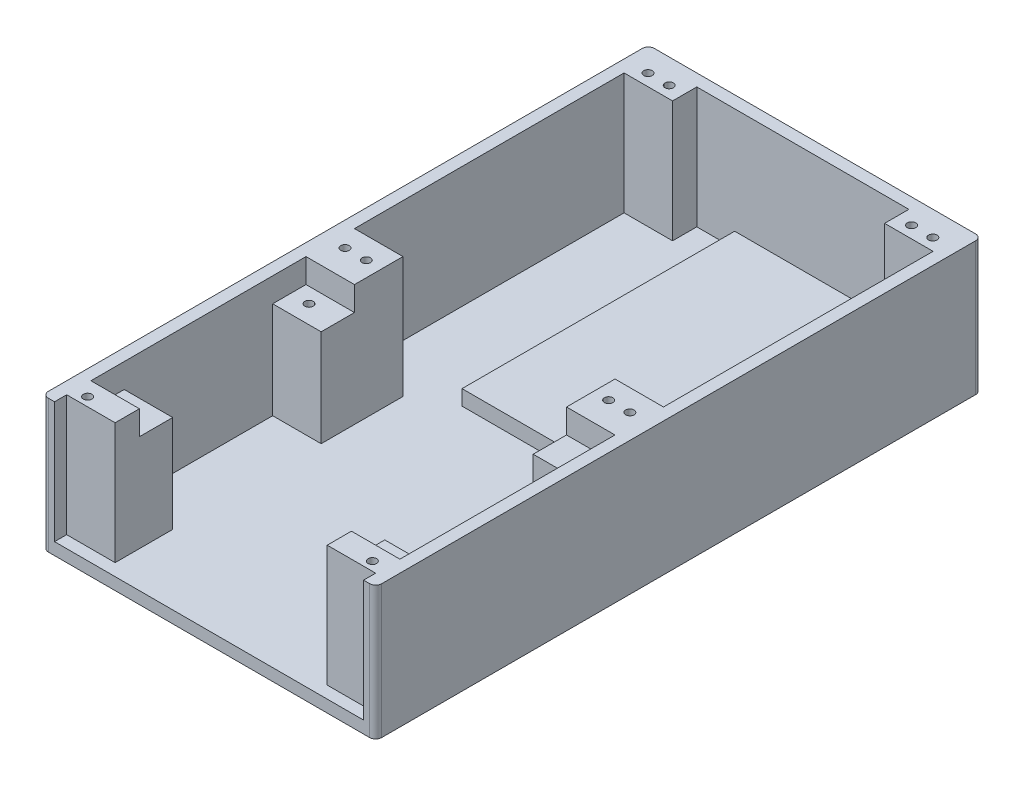
SolidWorks part; units mm, degrees
ref_plane "Front Plane" through (0, 0, 0) normal (0, 0, 1) x (1, 0, 0)
ref_plane "Top Plane" through (0, 0, 0) normal (0, 1, 0) x (1, 0, 0)
ref_plane "Right Plane" through (0, 0, 0) normal (1, 0, 0) x (0, 0, -1)
sketch "Sketch1" plane through (0, 0, 0) normal (0, 1, 0) x (1, 0, 0)
  line L1 (0, 0) -> (139.7, 0)
  line L2 (0, 0) -> (0, 254)
  line L3 (0, 254) -> (139.7, 254)
  line L4 (139.7, 0) -> (139.7, 254)
  dimension "D1" = 254
  dimension "D2" = 139.7
extrude "Base" add sketch "Sketch1" along normal blind 5.08
sketch "Sketch2" plane through (0, 5.08, 0) normal (0, 1, 0) x (1, 0, 0)
  line L1 (0, 254) -> (139.7, 254)
  line L2 (0, 254) -> (0, 0)
  line L3 (0, 0) -> (139.7, 0)
  line L4 (139.7, 254) -> (139.7, 0)
  line L5 (5.08, 248.92) -> (134.62, 248.92)
  line L6 (5.08, 248.92) -> (5.08, 5.08)
  line L7 (5.08, 5.08) -> (134.62, 5.08)
  line L8 (134.62, 248.92) -> (134.62, 5.08)
  line M9 (0, 254) -> (0, 0)
  line M10 (0, 0) -> (139.7, 0)
  line M11 (139.7, 0) -> (139.7, 254)
  line M12 (139.7, 254) -> (0, 254)
  dimension "D1" = 5.08
  dimension "D2" = 5.08
  dimension "D3" = 5.08
  dimension "D4" = 5.08
extrude "Walls" add sketch "Sketch2" along normal blind 50.8 contours L5 L8 L7 L6 M12 M9 M10 M11 region at (69.85, 5.08, -251.1012)
ref_plane "Plane1" through (0, 0, -60.96) normal (0, 0, 1) x (1, 0, 0)
sketch "Sketch4" plane through (0, 0, 0) normal (0, 0, 1) x (1, 0, 0)
  line L0 (0, 0) -> (139.7, 0) construction
  line L1 (5.08, 55.88) -> (134.62, 55.88)
  line L2 (5.08, 55.88) -> (5.08, 5.08)
  line L3 (5.08, 5.08) -> (134.62, 5.08)
  line L4 (134.62, 55.88) -> (134.62, 5.08)
  line L5 (0, 55.88) -> (0, 0) construction
  line L6 (139.7, 55.88) -> (139.7, 0) construction
  line L7 (0, 55.88) -> (139.7, 55.88) construction
  dimension "D1" = 5.08
  dimension "D2" = 5.08
  dimension "D3" = 5.08
  dimension "D4" = 0
extrude "Bottom Cut" cut sketch "Sketch4" against normal blind 139.7
sketch "Sketch12" plane through (0, 5.08, 0) normal (0, 1, 0) x (1, 0, 0)
  line L0 (139.7, 254) -> (0, 254) construction
  line L1 (134.62, 248.92) -> (114.3, 248.92)
  line L2 (134.62, 248.92) -> (134.62, 238.76)
  line L3 (134.62, 238.76) -> (114.3, 238.76)
  line L4 (114.3, 248.92) -> (114.3, 238.76)
  line L5 (139.7, 0) -> (139.7, 254) construction
  line L7 (5.08, 248.92) -> (25.4, 248.92)
  line L8 (5.08, 248.92) -> (5.08, 238.76)
  line L9 (5.08, 238.76) -> (25.4, 238.76)
  line L10 (25.4, 248.92) -> (25.4, 238.76)
  line L11 (134.62, 105.41) -> (114.3, 105.41)
  line L12 (134.62, 105.41) -> (134.62, 125.73)
  line L13 (134.62, 125.73) -> (114.3, 125.73)
  line L14 (114.3, 105.41) -> (114.3, 125.73)
  line L15 (5.08, 105.41) -> (25.4, 105.41)
  line L16 (5.08, 105.41) -> (5.08, 125.73)
  line L17 (5.08, 125.73) -> (25.4, 125.73)
  line L18 (25.4, 105.41) -> (25.4, 125.73)
  dimension "D1" = 15.24
  dimension "D2" = 25.4
  dimension "D3" = 20.32
extrude "Mounting Struts" add sketch "Sketch12" along normal up to surface (50.8 mm away) up to face at (69.85, 55.88, -125.73)
sketch "Sketch13" plane through (0, 55.88, 0) normal (0, 1, 0) x (1, 0, 0)
  line L0 (139.7, 254) -> (0, 254) construction
  line L1 (139.7, 0) -> (139.7, 254) construction
  circle A0 centre (120.65, 243.713) radius 1.778
  circle A1 centre (19.05, 243.713) radius 1.778
  circle A2 centre (120.65, 116.713) radius 1.778
  circle A3 centre (19.05, 116.713) radius 1.778
  dimension "D1" = 3.556
  dimension "D2" = 10.287
  dimension "D3" = 19.05
  dimension "D4" = 101.6
  dimension "D5" = 127
extrude "Panel Mounting Holes" cut sketch "Sketch13" against normal blind 12.7
sketch "Sketch14" plane through (0, 53.848, 0) normal (0, 1, 0) x (1, 0, 0)
  line L1 (134.62, 5.08) -> (114.3, 5.08)
  line L2 (134.62, 5.08) -> (134.62, 15.24)
  line L3 (134.62, 15.24) -> (114.3, 15.24)
  line L4 (114.3, 5.08) -> (114.3, 15.24)
  line L5 (5.08, 5.08) -> (25.4, 5.08)
  line L6 (5.08, 5.08) -> (5.08, 15.24)
  line L7 (5.08, 15.24) -> (25.4, 15.24)
  line L8 (25.4, 5.08) -> (25.4, 15.24)
  dimension "D1" = 10.16
  dimension "D2" = 20.32
extrude "Boss-Extrude6" add sketch "Sketch14" along normal up to surface and the other way up to surface up to face at (19.05, 55.88, -241.935) other way up to face at (69.85, 5.08, -148.59)
sketch "Sketch17" plane through (0, 55.88, 0) normal (0, 1, 0) x (1, 0, 0)
  line L0 (139.7, 0) -> (139.7, 254) construction
  line L1 (0, -30.734) -> (0, 30.734) construction
  circle A0 centre (129.54, 243.713) radius 1.778
  circle A1 centre (10.16, 243.713) radius 1.778
  circle A2 centre (10.16, 116.713) radius 1.778
  circle A3 centre (129.54, 116.713) radius 1.778
  circle A4 centre (129.54, 8.763) radius 1.778
  circle A5 centre (10.16, 8.763) radius 1.778
  circle A7 centre (120.65, 116.713) radius 1.778 construction
  circle A8 centre (19.05, 116.713) radius 1.778 construction
  circle A9 centre (19.05, 243.713) radius 1.778 construction
  circle A10 centre (120.65, 243.713) radius 1.778 construction
  dimension "D1" = 3.556
  dimension "D2" = 10.16
  dimension "D3" = 10.16
  dimension "D4" = 127
  dimension "D5" = 107.95
extrude "Front Mounting Holes" cut sketch "Sketch17" against normal blind 12.7
fillet "Corner Fillet" radius 2.54 4 edges at (0, 27.94, 0) (139.7, 27.94, 0) (0, 27.94, -254) (139.7, 27.94, -254)
sketch "Sketch18" plane through (0, 5.08, 0) normal (0, 1, 0) x (1, 0, 0)
  line L0 (25.4, 105.41) -> (25.4, 125.73) construction
  line L1 (5.08, 105.41) -> (25.4, 105.41)
  line L2 (5.08, 105.41) -> (5.08, 91.44)
  line L3 (5.08, 91.44) -> (25.4, 91.44)
  line L4 (25.4, 105.41) -> (25.4, 91.44)
  line L5 (134.62, 105.41) -> (114.3, 105.41)
  line L6 (134.62, 105.41) -> (134.62, 91.44)
  line L7 (134.62, 91.44) -> (114.3, 91.44)
  line L8 (114.3, 105.41) -> (114.3, 91.44)
  line L9 (134.62, 15.24) -> (114.3, 15.24)
  line L10 (134.62, 15.24) -> (134.62, 29.21)
  line L11 (134.62, 29.21) -> (114.3, 29.21)
  line L12 (114.3, 15.24) -> (114.3, 29.21)
  line L13 (5.08, 15.24) -> (25.4, 15.24)
  line L14 (5.08, 15.24) -> (5.08, 29.21)
  line L15 (5.08, 29.21) -> (25.4, 29.21)
  line L16 (25.4, 15.24) -> (25.4, 29.21)
  line L17 (114.3, 125.73) -> (114.3, 105.41) construction
  dimension "D1" = 13.97
extrude "Boss-Extrude8" add sketch "Sketch18" along normal blind 40.64
sketch "Sketch19" plane through (0, 45.72, 0) normal (0, 1, 0) x (1, 0, 0)
  line L0 (114.3, 105.41) -> (134.62, 105.41) construction
  line L1 (134.62, 105.41) -> (134.62, 15.24) construction
  line L2 (5.08, 15.24) -> (25.4, 15.24) construction
  line L3 (5.08, 105.41) -> (5.08, 15.24) construction
  circle A0 centre (12.7, 99.06) radius 1.778
  circle A1 centre (127, 99.06) radius 1.778
  circle A2 centre (127, 21.59) radius 1.778
  circle A3 centre (12.7, 21.59) radius 1.778
  dimension "D1" = 3.556
  dimension "D2" = 6.35
  dimension "D3" = 7.62
  dimension "D4" = 6.35
  dimension "D5" = 7.62
extrude "Cut-Extrude1" cut sketch "Sketch19" against normal blind 12.7
sketch "Sketch20" plane through (0, 5.08, 0) normal (0, 1, 0) x (1, 0, 0)
  line L0 (25.4, 248.92) -> (114.3, 248.92) construction
  line L1 (98.425, 248.92) -> (41.275, 248.92)
  line L2 (98.425, 248.92) -> (98.425, 134.62)
  line L3 (98.425, 134.62) -> (41.275, 134.62)
  line L4 (41.275, 248.92) -> (41.275, 134.62)
  line L6 (25.4, 238.76) -> (114.3, 238.76) construction
  point P10 (69.85, 238.76)
  point P11 (69.85, 248.92)
  dimension "D1" = 57.15
  dimension "D2" = 114.3
other "AlignGroup1"
extrude "Boss-Extrude9" add sketch "Sketch20" along normal blind 6.35
equation "\"Arrow Height\"= 1.5in"
equation "\"Button Height\"= 2in"
equation "\"Button Width\"= 4in"
equation "\"Haptic Diameter\"= 10mm"
equation "\"Haptic Thickness\"= 2.7mm"
equation "\"Arrow Spacing\"= 1in"
equation "\"Arrow Width\"= 1in"
equation "\"Haptic Wire Angle\"= 63.43"
equation "\"Haptic Wire Width\"= .1in"
equation "\"Haptic Wire Height\"= .15in"
equation "\"Mounting Bolt Hole Diameter\"= .14in"
equation "\"D1@Sketch13\"=\"Mounting Bolt Hole Diameter\""
equation "\"D1@Sketch17\"=\"Mounting Bolt Hole Diameter\""
equation "\"D1@Sketch19\"=\"Mounting Bolt Hole Diameter\""
